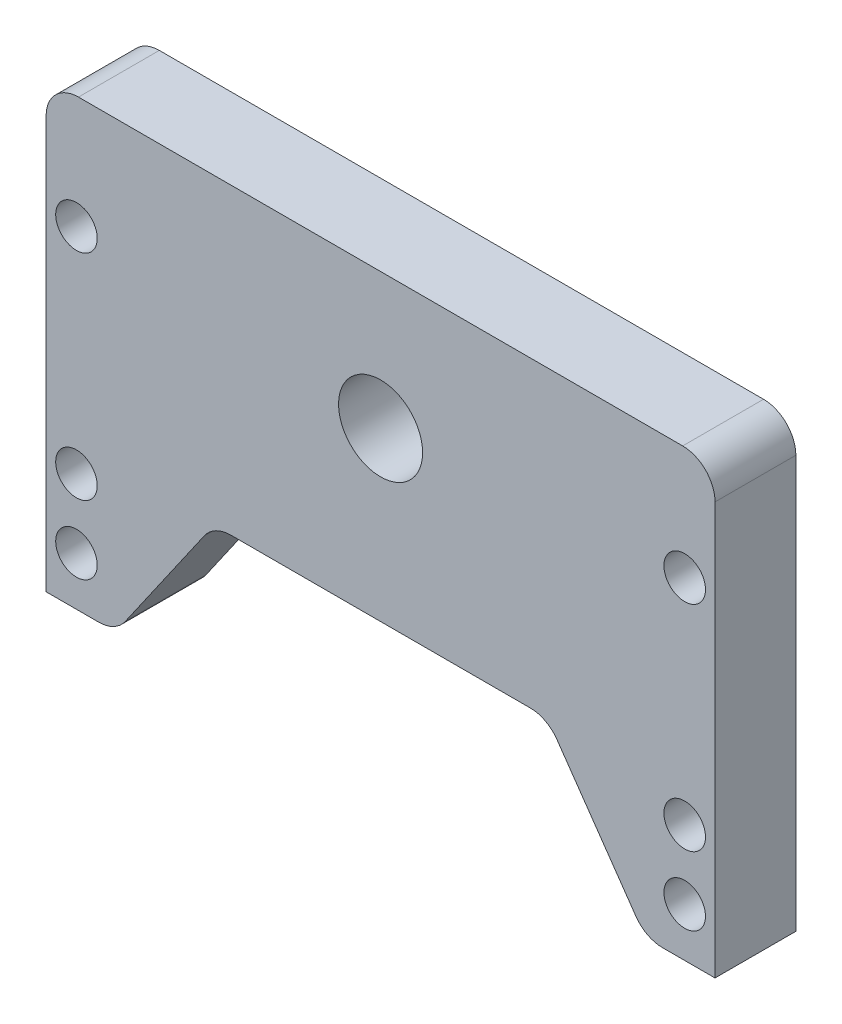
SolidWorks part; units mm, degrees
ref_plane "Front Plane" through (0, 0, 0) normal (0, 0, 1) x (1, 0, 0)
ref_plane "Top Plane" through (0, 0, 0) normal (0, 1, 0) x (1, 0, 0)
ref_plane "Right Plane" through (0, 0, 0) normal (1, 0, 0) x (0, 0, -1)
sketch "Sketch1" plane through (0, 0, 0) normal (0, 0, 1) x (1, 0, 0)
  line L0 (-26.27, -11.1125) -> (-22.1435, -11.1125)
  line L1 (-26.27, -11.1125) -> (-26.27, 21.2725)
  line L2 (-23.7299, 23.8125) -> (23.7299, 23.8125)
  line L3 (26.2699, 21.2725) -> (26.27, -11.1125)
  line L4 (26.27, -11.1125) -> (22.1435, -11.1125)
  line L5 (20.0581, -10.0226) -> (13.8467, -1.0899)
  line L6 (11.7613, 0) -> (-11.7613, 0)
  line L7 (-13.8467, -1.0899) -> (-20.0581, -10.0226)
  line L8 (0, -1000) -> (0, 49000) construction
  arc A0 (22.1435, -11.1125) -> (20.0581, -10.0226) centre (22.1435, -8.5725) cw
  arc A1 (-22.1435, -11.1125) -> (-20.0581, -10.0226) centre (-22.1435, -8.5725) ccw
  arc A2 (-11.7613, 0) -> (-13.8467, -1.0899) centre (-11.7613, -2.54) ccw
  arc A3 (13.8467, -1.0899) -> (11.7613, 0) centre (11.7613, -2.54) ccw
  arc A4 (-26.27, 21.2725) -> (-23.7299, 23.8125) centre (-23.7299, 21.2725) cw
  arc A5 (23.7299, 23.8125) -> (26.2699, 21.2725) centre (23.7299, 21.2725) cw
  circle A6 centre (23.8887, 14.9319) radius 1.632
  circle A7 centre (23.8887, -7.2931) radius 1.632
  circle A8 centre (-23.8887, -7.2931) radius 1.632
  circle A9 centre (-23.8887, 14.9319) radius 1.632
  circle A10 centre (23.8887, -1.8956) radius 1.632
  circle A11 centre (-23.8887, -1.8956) radius 1.632
  circle A12 centre (0, 13.1413) radius 3.3
  point P8 (0, 0)
  point P20 (-26.27, 23.8125)
  point P23 (26.2699, 23.8125)
  point P42 (0, 23.8125)
  dimension "D2" = 2.54
  dimension "D5" = 2.54
  dimension "D1" = 52.5399
  dimension "D3" = 11.1125
  dimension "D4" = 34.925
extrude "Boss-Extrude1" add sketch "Sketch1" along normal blind 6.35
